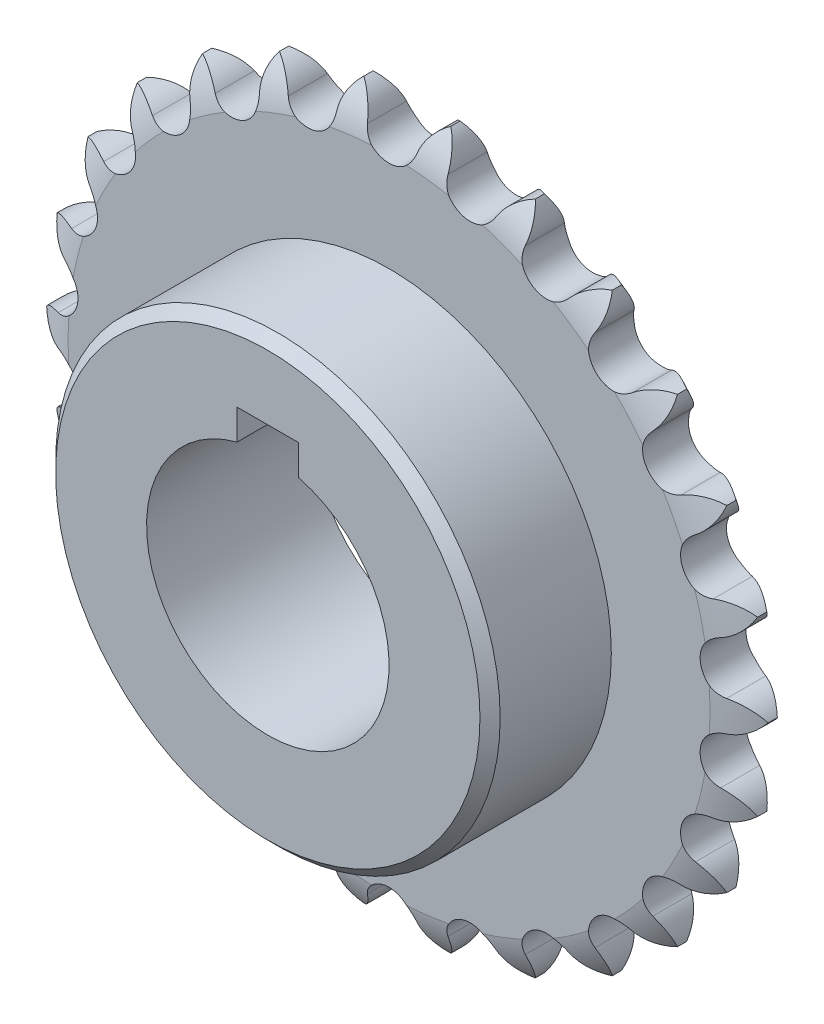
SolidWorks part; units mm, degrees
ref_plane "Front Plane" through (0, 0, 0) normal (0, 0, 1) x (1, 0, 0)
ref_plane "Top Plane" through (0, 0, 0) normal (0, 1, 0) x (1, 0, 0)
ref_plane "Right Plane" through (0, 0, 0) normal (1, 0, 0) x (0, 0, -1)
sketch "Sketch1" plane through (0, 0, 0) normal (0, 0, 1) x (1, 0, 0)
  line L0 (0, 0) -> (0, 56.7055) construction
  line L1 (0, 0) -> (9.6217, 51.1475) construction
  circle A0 centre (0, 0) radius 53.2892 construction
  circle A1 centre (0, 0) radius 49.2633 construction
  circle A2 centre (0, 0) radius 52.0446 construction
  circle A3 centre (0, 0) radius 19.05
  circle A4 centre (0, 0) radius 56.7055 construction
  arc A5 (-3.9297, 52.4145) -> (3.9297, 52.4145) centre (0, 53.2892) ccw
  arc A6 (3.9297, 52.4145) -> (6.8687, 56.288) centre (9.6217, 51.1475) cw
  arc A7 (-3.9297, 52.4145) -> (-6.8687, 56.288) centre (-9.6217, 51.1475) ccw
  arc A8 (8.7281, 51.8318) -> (6.8015, 56.2961) centre (2.8983, 51.9638) ccw
  arc A9 (8.7281, 51.8318) -> (16.3591, 49.951) centre (12.7529, 51.7407) ccw
  arc A10 (16.3591, 49.951) -> (20.1397, 53.0086) centre (21.5825, 47.3586) cw
  arc A11 (20.8786, 48.2369) -> (20.0764, 53.0326) centre (15.2499, 49.7602) ccw
  arc A12 (20.8786, 48.2369) -> (27.8378, 44.5845) centre (24.7647, 47.1852) ccw
  arc A13 (27.8378, 44.5845) -> (32.2402, 46.6485) centre (32.289, 40.8174) cw
  arc A14 (31.8158, 41.8387) -> (32.1845, 46.6869) centre (26.7151, 44.6648) ccw
  arc A15 (31.8158, 41.8387) -> (37.6987, 36.6269) centre (35.3373, 39.8875) ccw
  arc A16 (37.6987, 36.6269) -> (42.4671, 37.5774) centre (41.119, 31.9041) cw
  arc A17 (40.9039, 33.0089) -> (42.4222, 37.628) centre (36.6278, 36.9736) ccw
  arc A18 (40.9039, 33.0089) -> (45.3686, 26.5407) centre (43.8562, 30.2717) ccw
  arc A19 (45.3686, 26.5407) -> (50.2259, 26.3224) centre (47.5593, 21.1366) cw
  arc A20 (47.6149, 22.2608) -> (50.1945, 26.3823) centre (44.4118, 27.1336) ccw
  arc A21 (47.6149, 22.2608) -> (50.4019, 14.9121) centre (49.8263, 18.8966) ccw
  arc A22 (50.4019, 14.9121) -> (55.0658, 13.5376) centre (51.2356, 9.1407) cw
  arc A23 (51.5586, 10.2189) -> (55.0496, 13.6034) centre (49.6148, 15.7167) ccw
  arc A24 (51.5586, 10.2189) -> (52.506, 2.4168) centre (52.9007, 6.4233) ccw
  arc A25 (52.506, 2.4168) -> (56.7055, -0.0338) centre (51.9343, -3.3864) cw
  arc A26 (52.506, -2.4168) -> (56.7055, 0.0338) centre (51.9343, 3.3864) ccw
  arc A27 (52.506, -2.4168) -> (51.5586, -10.2189) centre (52.9007, -6.4233) ccw
  arc A28 (51.5586, -10.2189) -> (55.0496, -13.6034) centre (49.6148, -15.7167) cw
  arc A29 (50.4019, -14.9121) -> (55.0658, -13.5376) centre (51.2356, -9.1407) ccw
  arc A30 (50.4019, -14.9121) -> (47.6149, -22.2608) centre (49.8263, -18.8966) ccw
  arc A31 (47.6149, -22.2608) -> (50.1945, -26.3823) centre (44.4118, -27.1336) cw
  arc A32 (45.3686, -26.5407) -> (50.2259, -26.3224) centre (47.5593, -21.1366) ccw
  arc A33 (45.3686, -26.5407) -> (40.9039, -33.0089) centre (43.8562, -30.2717) ccw
  arc A34 (40.9039, -33.0089) -> (42.4222, -37.628) centre (36.6278, -36.9736) cw
  arc A35 (37.6987, -36.6269) -> (42.4671, -37.5774) centre (41.119, -31.9041) ccw
  arc A36 (37.6987, -36.6269) -> (31.8158, -41.8387) centre (35.3373, -39.8875) ccw
  arc A37 (31.8158, -41.8387) -> (32.1845, -46.6869) centre (26.7151, -44.6648) cw
  arc A38 (27.8378, -44.5845) -> (32.2402, -46.6485) centre (32.289, -40.8174) ccw
  arc A39 (27.8378, -44.5845) -> (20.8786, -48.2369) centre (24.7647, -47.1852) ccw
  arc A40 (20.8786, -48.2369) -> (20.0764, -53.0326) centre (15.2499, -49.7602) cw
  arc A41 (16.3591, -49.951) -> (20.1397, -53.0086) centre (21.5825, -47.3586) ccw
  arc A42 (16.3591, -49.951) -> (8.7281, -51.8318) centre (12.7529, -51.7407) ccw
  arc A43 (8.7281, -51.8318) -> (6.8015, -56.2961) centre (2.8983, -51.9638) cw
  arc A44 (3.9297, -52.4145) -> (6.8687, -56.288) centre (9.6217, -51.1475) ccw
  arc A45 (3.9297, -52.4145) -> (-3.9297, -52.4145) centre (0, -53.2892) ccw
  arc A46 (-3.9297, -52.4145) -> (-6.8687, -56.288) centre (-9.6217, -51.1475) cw
  arc A47 (-8.7281, -51.8318) -> (-6.8015, -56.2961) centre (-2.8983, -51.9638) ccw
  arc A48 (-8.7281, -51.8318) -> (-16.3591, -49.951) centre (-12.7529, -51.7407) ccw
  arc A49 (-16.3591, -49.951) -> (-20.1397, -53.0086) centre (-21.5825, -47.3586) cw
  arc A50 (-20.8786, -48.2369) -> (-20.0764, -53.0326) centre (-15.2499, -49.7602) ccw
  arc A51 (-20.8786, -48.2369) -> (-27.8378, -44.5845) centre (-24.7647, -47.1852) ccw
  arc A52 (-27.8378, -44.5845) -> (-32.2402, -46.6485) centre (-32.289, -40.8174) cw
  arc A53 (-31.8158, -41.8387) -> (-32.1845, -46.6869) centre (-26.7151, -44.6648) ccw
  arc A54 (-31.8158, -41.8387) -> (-37.6987, -36.6269) centre (-35.3373, -39.8875) ccw
  arc A55 (-37.6987, -36.6269) -> (-42.4671, -37.5774) centre (-41.119, -31.9041) cw
  arc A56 (-40.9039, -33.0089) -> (-42.4222, -37.628) centre (-36.6278, -36.9736) ccw
  arc A57 (-40.9039, -33.0089) -> (-45.3686, -26.5407) centre (-43.8562, -30.2717) ccw
  arc A58 (-45.3686, -26.5407) -> (-50.2259, -26.3224) centre (-47.5593, -21.1366) cw
  arc A59 (-47.6149, -22.2608) -> (-50.1945, -26.3823) centre (-44.4118, -27.1336) ccw
  arc A60 (-47.6149, -22.2608) -> (-50.4019, -14.9121) centre (-49.8263, -18.8966) ccw
  arc A61 (-50.4019, -14.9121) -> (-55.0658, -13.5376) centre (-51.2356, -9.1407) cw
  arc A62 (-51.5586, -10.2189) -> (-55.0496, -13.6034) centre (-49.6148, -15.7167) ccw
  arc A63 (-51.5586, -10.2189) -> (-52.506, -2.4168) centre (-52.9007, -6.4233) ccw
  arc A64 (-52.506, -2.4168) -> (-56.7055, 0.0338) centre (-51.9343, 3.3864) cw
  arc A65 (-52.506, 2.4168) -> (-56.7055, -0.0338) centre (-51.9343, -3.3864) ccw
  arc A66 (-52.506, 2.4168) -> (-51.5586, 10.2189) centre (-52.9007, 6.4233) ccw
  arc A67 (-51.5586, 10.2189) -> (-55.0496, 13.6034) centre (-49.6148, 15.7167) cw
  arc A68 (-50.4019, 14.9121) -> (-55.0658, 13.5376) centre (-51.2356, 9.1407) ccw
  arc A69 (-50.4019, 14.9121) -> (-47.6149, 22.2608) centre (-49.8263, 18.8966) ccw
  arc A70 (-47.6149, 22.2608) -> (-50.1945, 26.3823) centre (-44.4118, 27.1336) cw
  arc A71 (-45.3686, 26.5407) -> (-50.2259, 26.3224) centre (-47.5593, 21.1366) ccw
  arc A72 (-45.3686, 26.5407) -> (-40.9039, 33.0089) centre (-43.8562, 30.2717) ccw
  arc A73 (-40.9039, 33.0089) -> (-42.4222, 37.628) centre (-36.6278, 36.9736) cw
  arc A74 (-37.6987, 36.6269) -> (-42.4671, 37.5774) centre (-41.119, 31.9041) ccw
  arc A75 (-37.6987, 36.6269) -> (-31.8158, 41.8387) centre (-35.3373, 39.8875) ccw
  arc A76 (-31.8158, 41.8387) -> (-32.1845, 46.6869) centre (-26.7151, 44.6648) cw
  arc A77 (-27.8378, 44.5845) -> (-32.2402, 46.6485) centre (-32.289, 40.8174) ccw
  arc A78 (-27.8378, 44.5845) -> (-20.8786, 48.2369) centre (-24.7647, 47.1852) ccw
  arc A79 (-20.8786, 48.2369) -> (-20.0764, 53.0326) centre (-15.2499, 49.7602) cw
  arc A80 (-16.3591, 49.951) -> (-20.1397, 53.0086) centre (-21.5825, 47.3586) ccw
  arc A81 (-16.3591, 49.951) -> (-8.7281, 51.8318) centre (-12.7529, 51.7407) ccw
  arc A82 (-8.7281, 51.8318) -> (-6.8015, 56.2961) centre (-2.8983, 51.9638) cw
  point P192 (0, 0)
  dimension "D1" = 113.411
  dimension "D2" = 106.5784
  dimension "D3" = 104.0892
  dimension "D4" = 98.5266
  dimension "D5" = 5.8313
  dimension "D6" = 38.1
  dimension "D7" = 26
extrude "Boss-Extrude2" add sketch "Sketch1" along normal blind 7.213 contours A82 A81 A80 A79 A78 A77 A76 A75 A74 A73 A72 A71 A70 A69 A68 A67 A66 A65 A64 A63 A62 A61 A60 A59 A58 A57 A56 A55 A54 A53 A52 A51 A50 A49 A48 A47 A46 A45 A44 A43 A42 A41 A40 A39 A38 A37 A36 A35 A34 A33 A32 region at (0, 47.6659, 0)
sketch "Sketch2" plane through (0, 0, 0) normal (1, 0, 0) x (0, 0, -1)
  line L0 (-7.213, 41.8387) -> (-7.213, 35.8616) construction
  line L1 (-7.213, 19.05) -> (-26.263, 19.05)
  line L2 (-7.213, 19.05) -> (-7.213, 34.925)
  line L3 (-7.213, 34.925) -> (-26.263, 34.925)
  line L4 (-26.263, 19.05) -> (-26.263, 34.925)
  line L5 (0, 0) -> (-33.1926, 0) construction
  dimension "D1" = 19.05
  dimension "D2" = 38.1
  dimension "D3" = 69.85
revolve "Revolve1" add sketch "Sketch2" angle 360 about L5
sketch "Sketch3" plane through (0, 0, 26.263) normal (0, 0, 1) x (1, 0, 0)
  line L0 (0, 0) -> (0, 25.5373) construction
  line L2 (-4.826, 18.4286) -> (4.826, 18.4286)
  line L3 (-4.826, 18.4286) -> (-4.826, 23.1911)
  line L4 (-4.826, 23.1911) -> (4.826, 23.1911)
  line L5 (4.826, 18.4286) -> (4.826, 23.1911)
  circle A0 centre (0, 0) radius 19.05 construction
  dimension "D1" = 9.652
  dimension "D2" = 4.7625
extrude "Cut-Extrude1" cut sketch "Sketch3" against normal through all contours L3 L2 L5 L4
sketch "Sketch4" plane through (0, 0, 0) normal (1, 0, 0) x (0, 0, -1)
  line L0 (-3.6065, 56.2683) -> (-3.6065, 43.0404) construction
  line L1 (-7.213, 56.2683) -> (0, 56.2683) construction
  line L2 (-7.213, 50.419) -> (-13.8497, 50.419)
  line L3 (-7.213, 46.648) -> (-7.213, 41.8387) construction
  line L4 (-13.8497, 50.419) -> (-13.8497, 56.89)
  line L5 (-13.8497, 56.89) -> (-4.1486, 56.89)
  line L6 (6.6367, 56.89) -> (-3.0644, 56.89)
  line L7 (6.6367, 50.419) -> (6.6367, 56.89)
  line L8 (0, 50.419) -> (6.6367, 50.419)
  line L9 (0, 0) -> (10.4409, 0) construction
  arc A0 (-4.1486, 56.89) -> (-7.213, 50.419) centre (5.3318, 48.4394) ccw
  arc A1 (-3.0644, 56.89) -> (0, 50.419) centre (-12.5448, 48.4394) cw
  dimension "D3" = 12.7
  dimension "D1" = 50.419
  dimension "D2" = 56.89
revolve "Cut-Revolve1" cut sketch "Sketch4" angle 360 about L9 region at (0, 53.8624, 9.9059)
chamfer "Chamfer1" distance 1.5875 angle 45 1 edges at (-34.925, 0, 26.263)
ref_axis "Axis1" through (0, 0, 26.263) along (0, 0, -1)
